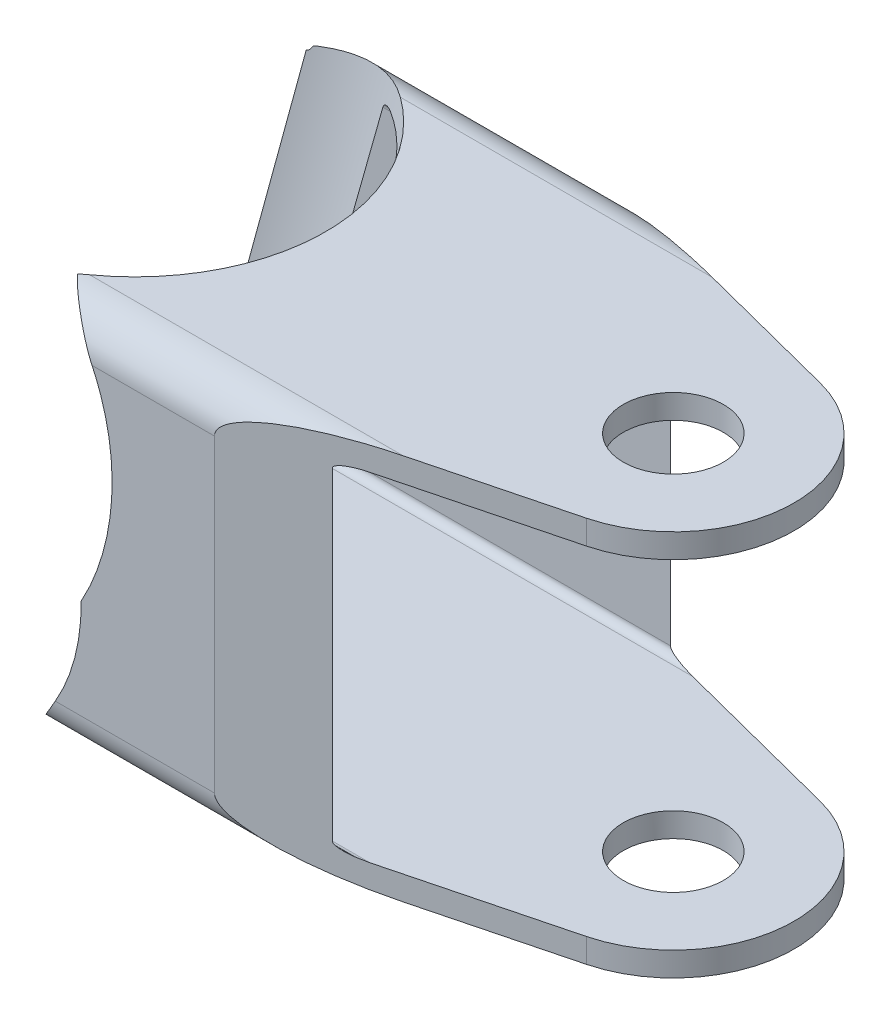
SolidWorks part; units mm, degrees
note: '?' marks a value the reader was unsure of.
material "AISI 4130 Steel, annealed at 865C"
ref_plane "Front Plane" through (0, 0, 0) normal (0, 0, 1) x (1, 0, 0)
ref_plane "Top Plane" through (0, 0, 0) normal (0, 1, 0) x (1, 0, 0)
ref_plane "Right Plane" through (0, 0, 0) normal (1, 0, 0) x (0, 0, -1)
sketch "Sketch1" plane through (0, 0, 0) normal (1, 0, 0) x (0, 0, -1)
  line L1 (-10.16, 12.7) -> (10.16, 12.7)
  line L2 (-12.7, 10.16) -> (-12.7, -10.16)
  line L3 (-10.16, -12.7) -> (10.16, -12.7)
  line L4 (12.7, 10.16) -> (12.7, -10.16)
  arc A0 (-10.16, 12.7) -> (-12.7, 10.16) centre (-10.16, 10.16) ccw
  arc A1 (-10.16, -12.7) -> (-12.7, -10.16) centre (-10.16, -10.16) cw
  arc A2 (10.16, 12.7) -> (12.7, 10.16) centre (10.16, 10.16) cw
  arc A3 (12.7, -10.16) -> (10.16, -12.7) centre (10.16, -10.16) cw
  point P4 (0, -12.7)
  point P7 (0, 0)
  point P15 (12.7, 0)
  dimension "D3" = 2.54
  dimension "D4" = 2.54
  dimension "D5" = 2.54
  dimension "D6" = 2.54
  dimension "D1" = 25.4
  dimension "D2" = 20.32
extrude "Boss-Extrude1" add sketch "Sketch1" along normal blind 25.4 and the other way blind 34.925
sketch "Sketch11" plane through (25.4, 0, 0) normal (1, 0, 0) x (0, 0, -1)
  line L0 (-10.16, -12.7) -> (10.16, -12.7) construction
  line L1 (-10.6045, 11.1125) -> (10.6045, 11.1125)
  line L2 (-11.1125, 10.6045) -> (-11.1125, -10.6045)
  line L3 (-10.6045, -11.1125) -> (10.6045, -11.1125)
  line L4 (11.1125, 10.6045) -> (11.1125, -10.6045)
  line L5 (10.16, 12.7) -> (-10.16, 12.7) construction
  line L6 (12.7, -10.16) -> (12.7, 10.16) construction
  line L7 (-12.7, 10.16) -> (-12.7, -10.16) construction
  arc A0 (10.6045, 11.1125) -> (11.1125, 10.6045) centre (10.6045, 10.6045) cw
  arc A1 (10.6045, -11.1125) -> (11.1125, -10.6045) centre (10.6045, -10.6045) ccw
  arc A2 (-11.1125, -10.6045) -> (-10.6045, -11.1125) centre (-10.6045, -10.6045) ccw
  arc A3 (-10.6045, 11.1125) -> (-11.1125, 10.6045) centre (-10.6045, 10.6045) ccw
  dimension "D1" = 1.5875
  dimension "D2" = 1.5875
  dimension "D3" = 1.5875
  dimension "D4" = 1.5875
  dimension "D5" = 0.508
extrude "Cut-Extrude4" cut sketch "Sketch11" against normal through all
sketch "Sketch12" plane through (0, 12.7, 0) normal (0, 1, 0) x (1, 0, 0)
  line L1 (0, 12.7) -> (50.8, 12.7)
  line L2 (50.8, 12.7) -> (50.8, -12.7)
  line L12 (50.8, -12.7) -> (0, -12.7)
  line L13 (19.4444, -7.6861) -> (0, -12.7)
  line L14 (19.4444, 7.6861) -> (0, 12.7)
  line L15 (-34.925, -12.7) -> (25.4, -12.7) construction
  line L16 (-34.925, 12.7) -> (25.4, 12.7) construction
  line L18 (25.4, 10.16) -> (25.4, -10.16) construction
  arc A1 (19.4444, -7.6861) -> (19.4444, 7.6861) centre (17.4625, 0) ccw
  point P8 (18.1688, 9.2165)
  dimension "D2" = 50.8
  dimension "D1" = 17.4625
extrude "Cut-Extrude5" cut sketch "Sketch12" against normal through all
sketch "Sketch14" plane through (0, 12.7, 0) normal (0, 1, 0) x (1, 0, 0)
  circle A0 centre (17.4625, 0) radius 3.2893
  arc A2 (19.4444, -7.6861) -> (19.4444, 7.6861) centre (17.4625, 0) ccw construction
  point P0 (17.4625, 0)
  point P6 (25.4, 0)
  dimension "D2" = 6.5786
  dimension "D1" = 7.9375
  dimension "D3" = 17.4625
extrude "Cut-Extrude6" cut sketch "Sketch14" against normal through all
ref_axis "Axis1" through (-76.1607, 10.6803, 0.1041) along (0.9661, -0.2581, 0)?
ref_axis "Axis2" through (-72.0904, 10.0753, 62.0547) along (0.6127, -0.1697, -0.7719)?
ref_axis "Axis3" through (-14.5245, -5.1858, 76.9148) along (-0.1086, 0.0213, -0.9939)?
ref_axis "Axis4" through (-5.7422, 30.6897, 69.6754) along (-0.2163, -0.431, -0.876)?
ref_axis "Axis5" through (-6.826, 56.7068, -0.3649) along (-0.2581, -0.9661, 0.0075)?
ref_point "Point1"
ref_point "Point2"
ref_point "Point3"
ref_point "Point4"
ref_point "Point5"
ref_plane "Plane1" through (-34.925, -0.3344, 0.1041) normal (0.9661, -0.2581, 0) x (0, 0, -1)
ref_plane "Plane2" through (-32.9168, -0.7728, 12.7) normal (0.6127, -0.1697, -0.7719) x (-0.7903, -0.1315, -0.5984)
ref_plane "Plane3" through (-21.5426, -3.811, 12.7) normal (-0.1086, 0.0213, -0.9939) x (-0.9941, -0.0023, 0.1086)
ref_plane "Plane4" through (-19.8094, 2.6562, 12.7) normal (-0.2163, -0.431, -0.876) x (-0.9763, 0.0955, 0.1941)
ref_plane "Plane5" through (-18.5809, 12.7, -0.0223) normal (-0.2581, -0.9661, 0.0075) x (-0.9661, 0.2581, -0.002)
sketch "Sketch16" plane through (-34.925, -0.3344, 0.1041) normal (0.9661, -0.2581, 0) x (0, 0, -1)
  circle A0 centre (0, 0) radius 12.7
sketch "Sketch17" plane through (-32.9168, -0.7728, 12.7) normal (0.6127, -0.1697, -0.7719) x (-0.7903, -0.1315, -0.5984)
  circle A0 centre (0, 0) radius 12.7
sketch "Sketch18" plane through (-21.5426, -3.811, 12.7) normal (-0.1086, 0.0213, -0.9939) x (-0.9941, -0.0023, 0.1086)
  circle A0 centre (0, 0) radius 12.7
sketch "Sketch19" plane through (-19.8094, 2.6562, 12.7) normal (-0.2163, -0.431, -0.876) x (-0.9763, 0.0955, 0.1941)
  circle A0 centre (0, 0) radius 12.7
sketch "Sketch20" plane through (-18.5809, 12.7, -0.0223) normal (-0.2581, -0.9661, 0.0075) x (-0.9661, 0.2581, -0.002)
  circle A0 centre (0, 0) radius 12.7
extrude "Cut-Extrude7" cut sketch "Sketch16" against normal blind 12.7 and the other way blind 11.43
extrude "Cut-Extrude9" cut sketch "Sketch17" against normal blind 12.7 and the other way blind 4.445
extrude "Cut-Extrude10" cut sketch "Sketch18" against normal blind 12.7 and the other way blind 11.684 body kept at (-30.0495, 11.5914, 12.2582)
extrude "Cut-Extrude11" cut sketch "Sketch19" against normal blind 12.7 and the other way blind 8.128
extrude "Cut-Extrude12" cut sketch "Sketch20" against normal blind 12.7 and the other way blind 35.814
ref_plane "Plane6" through (-20.5099, 5.4785, 0) normal (-0.9661, 0.2581, 0) x (-0.2581, -0.9661, 0.0075)
sketch "Sketch23" plane through (-20.5099, 5.4785, 0) normal (-0.9661, 0.2581, 0) x (-0.2581, -0.9661, 0.0075)
  line L1 (-18.212, 20.3882) -> (25.7273, 20.3882)
  line L2 (-18.212, 20.3882) -> (-18.212, -17.8782)
  line L3 (-18.212, -17.8782) -> (25.7273, -17.8782)
  line L4 (25.7273, 20.3882) -> (25.7273, -17.8782)
extrude "Cut-Extrude13" cut sketch "Sketch23" along normal through all
